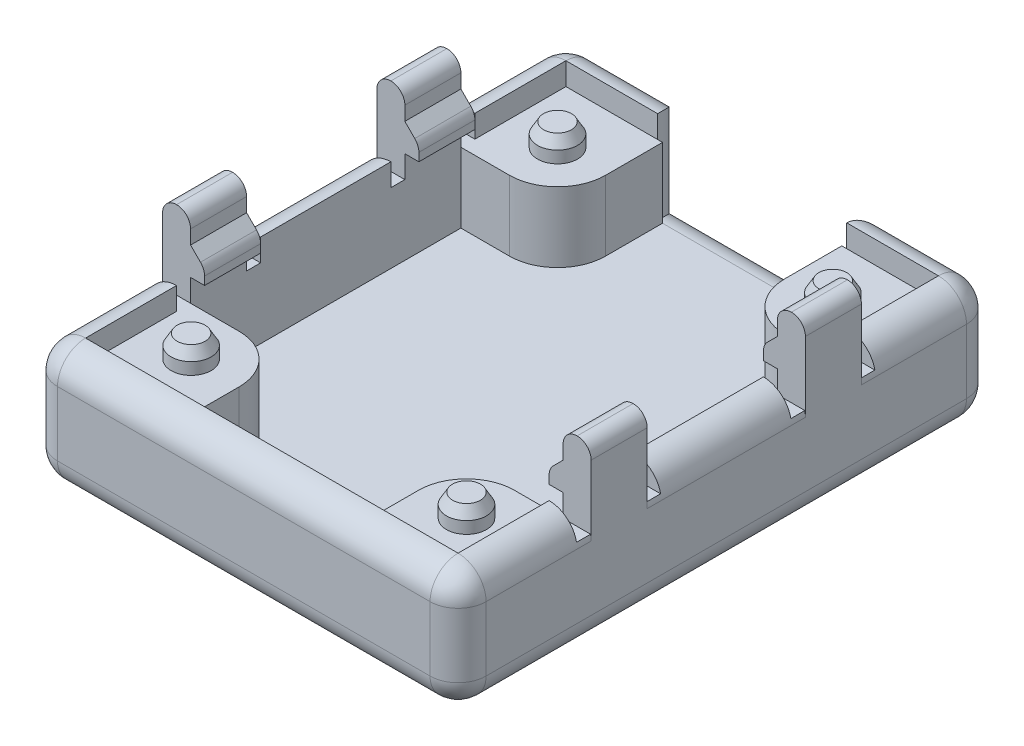
SolidWorks part; units mm, degrees
ref_plane "Front Plane" through (0, 0, 0) normal (0, 0, 1) x (1, 0, 0)
ref_plane "Top Plane" through (0, 0, 0) normal (0, 1, 0) x (1, 0, 0)
ref_plane "Right Plane" through (0, 0, 0) normal (1, 0, 0) x (0, 0, -1)
sketch "top right screw hole" plane through (0, 0, 0) normal (0, 1, 0) x (1, 0, 0)
  line L0 (-8.4, 0) -> (8.4, 0) construction
  line L1 (0, 11.65) -> (0, -11.65) construction
  circle A0 centre (9.83, 13.08) radius 1.43
  point P2 (0, 0)
  point P6 (0, 0)
  point P9 (9.83, 11.65)
  point P10 (8.4, 13.08)
  point P11 (0, 0)
  point P12 (0, 0)
  point P13 (0, 0)
  dimension "D3" = 2.86
  dimension "D1" = 16.8
  dimension "D2" = 23.3
sketch "all screw holes" plane through (0, 0, 0) normal (0, 1, 0) x (1, 0, 0)
  line L0 (0, -4.73) -> (0, 4.73) construction
  line L1 (-4.73, 0) -> (4.73, 0) construction
  circle A0 centre (9.83, 13.08) radius 1.43 construction
  circle A1 centre (9.83, 13.08) radius 1.43
  circle A2 centre (-9.83, 13.08) radius 1.43
  circle A3 centre (-9.83, -13.08) radius 1.43
  circle A4 centre (9.83, -13.08) radius 1.43
  point P13 (0, 0)
sketch "pcb" plane through (0, 0, 0) normal (0, 1, 0) x (1, 0, 0)
  line L1 (-13.3, -17.15) -> (13.3, -17.15)
  line L2 (-13.3, -17.15) -> (-13.3, 17.15)
  line L3 (-13.3, 17.15) -> (13.3, 17.15)
  line L4 (13.3, -17.15) -> (13.3, 17.15)
  line L5 (-13.3, -17.15) -> (13.3, 17.15) construction
  line L6 (-13.3, 17.15) -> (13.3, -17.15) construction
  point P0 (0, 0)
  point P6 (0, 0)
  dimension "D1" = 26.6
  dimension "D2" = 34.3
sketch "wires" plane through (0, 0, 0) normal (0, 1, 0) x (1, 0, 0)
  line L0 (-13.3, 17.15) -> (13.3, 17.15) construction
  line L1 (-6.75, 17.15) -> (6.75, 17.15)
  line L2 (-6.75, 17.15) -> (-6.75, 21.7884)
  line L3 (-6.75, 21.7884) -> (6.75, 21.7884)
  line L4 (6.75, 17.15) -> (6.75, 21.7884)
  line L5 (-6.75, 17.15) -> (6.75, 21.7884) construction
  line L6 (-6.75, 21.7884) -> (6.75, 17.15) construction
  point P0 (0, 19.4692)
  point P5 (0, 0)
  point P6 (0, 0)
  point P8 (0, 0)
  point P9 (0, 22.0718)
  point P12 (0, 0)
  dimension "D1" = 13.5
sketch "room for bottom wires" plane through (0, 0, 0) normal (1, 0, 0) x (0, 0, -1)
  line L0 (-17.15, 0) -> (17.15, 0) construction
  line L1 (-17.15, 0) -> (17.15, 0)
  line L2 (-17.15, 0) -> (-17.15, -5)
  line L3 (-17.15, -5) -> (17.15, -5)
  line L4 (17.15, 0) -> (17.15, -5)
  line L5 (-17.15, 0) -> (17.15, 0) construction
  point P8 (0, 0)
  point P10 (0, 0)
  point P12 (0, 0)
  dimension "D1" = 5
sketch "Sketch6" plane through (0, 0, 0) normal (0, 1, 0) x (1, 0, 0)
  line L8 (-15.3, -19.15) -> (15.3, -19.15)
  line L9 (15.3, -19.15) -> (15.3, 19.15)
  line L10 (15.3, 19.15) -> (-15.3, 19.15)
  line L11 (-15.3, 19.15) -> (-15.3, -19.15)
  line L12 (-15.3, -19.15) -> (15.3, -19.15)
  line L13 (15.3, -19.15) -> (15.3, 19.15)
  line L14 (15.3, 19.15) -> (-15.3, 19.15)
  line L15 (-15.3, 19.15) -> (-15.3, -19.15)
  dimension "D1" = 2
extrude "base" add sketch "Sketch6" against normal blind 2 from vertex at -5 starting at point (0, -5, 17.15)
sketch "pcb thickness" plane through (0, 0, 0) normal (1, 0, 0) x (0, 0, -1)
  line L0 (16.83, 0) -> (-16.83, 0) construction
  line L1 (-17.15, 0) -> (17.15, 0)
  line L2 (-17.15, 0) -> (-17.15, 1.6)
  line L3 (-17.15, 1.6) -> (17.15, 1.6)
  line L4 (17.15, 0) -> (17.15, 1.6)
  line L5 (-17.15, 0) -> (17.15, 1.6) construction
  line L6 (-17.15, 1.6) -> (17.15, 0) construction
  point P0 (0, 0.8)
  point P9 (0, 0)
  point P10 (0, 0)
  dimension "D1" = 1.6
sketch "Sketch8" plane through (0, -5, 0) normal (0, 1, 0) x (1, 0, 0)
  line L0 (6.75, 17.15) -> (6.75, 21.7884) construction
  line L1 (-6.75, 17.15) -> (-6.75, 21.7884) construction
  line L2 (6.75, 17.15) -> (6.75, 19.15)
  line L3 (-6.75, 17.15) -> (-6.75, 19.15)
  line L4 (-15.3, 19.15) -> (-15.3, -19.15)
  line L5 (-15.3, -19.15) -> (15.3, -19.15)
  line L6 (15.3, -19.15) -> (15.3, 19.15)
  line L7 (15.3, 19.15) -> (-15.3, 19.15)
  line L8 (-15.3, 19.15) -> (-15.3, -19.15)
  line L9 (-15.3, -19.15) -> (15.3, -19.15)
  line L10 (15.3, -19.15) -> (15.3, 19.15)
  line L11 (15.3, 19.15) -> (6.75, 19.15)
  line L12 (-13.3, -17.15) -> (13.3, -17.15)
  line L13 (13.3, -17.15) -> (13.3, 17.15)
  line L14 (13.3, 17.15) -> (-13.3, 17.15)
  line L15 (-13.3, 17.15) -> (-13.3, -17.15)
  line L16 (-13.3, -17.15) -> (13.3, -17.15)
  line L17 (13.3, -17.15) -> (13.3, 17.15)
  line L18 (13.3, 17.15) -> (6.75, 17.15)
  line L19 (-13.3, 17.15) -> (-13.3, -17.15)
  line L20 (-6.75, 19.15) -> (-15.3, 19.15)
  line L21 (-6.75, 17.15) -> (-13.3, 17.15)
  dimension "D1" = 0
  dimension "D2" = 0
extrude "walls" add sketch "Sketch8" along normal up to vertex (6.6 mm away) up to point (0, 1.6, -17.15)
sketch "Sketch9" plane through (0, 0, 0) normal (0, 1, 0) x (1, 0, 0)
  line L0 (6.4, 13.08) -> (6.4, 17.15)
  line L2 (-13.3, 17.15) -> (13.3, 17.15) construction
  line L4 (6.4, 17.15) -> (13.3, 17.15)
  line L5 (13.3, 17.15) -> (13.3, 9.65)
  line L6 (13.3, -17.15) -> (13.3, 17.15) construction
  line L7 (13.3, 9.65) -> (9.83, 9.65)
  line L8 (0, -4.73) -> (0, 4.73) construction
  line L9 (-13.3, 9.65) -> (-9.83, 9.65)
  line L10 (-13.3, 17.15) -> (-13.3, 9.65)
  line L11 (-6.4, 17.15) -> (-13.3, 17.15)
  line L12 (-6.4, 13.08) -> (-6.4, 17.15)
  line L13 (-4.73, 0) -> (4.73, 0) construction
  line L14 (-6.4, -13.08) -> (-6.4, -17.15)
  line L15 (-6.4, -17.15) -> (-13.3, -17.15)
  line L16 (-13.3, -17.15) -> (-13.3, -9.65)
  line L17 (-13.3, -9.65) -> (-9.83, -9.65)
  line L18 (13.3, -9.65) -> (9.83, -9.65)
  line L19 (13.3, -17.15) -> (13.3, -9.65)
  line L20 (6.4, -17.15) -> (13.3, -17.15)
  line L21 (6.4, -13.08) -> (6.4, -17.15)
  arc A5 (-6.4, 13.08) -> (-9.83, 9.65) centre (-9.83, 13.08) cw
  circle A10 centre (9.83, 13.08) radius 3.43
  arc A12 (6.4, 13.08) -> (9.83, 9.65) centre (9.83, 13.08) ccw
  arc A13 (6.4, -13.08) -> (9.83, -9.65) centre (9.83, -13.08) cw
  arc A15 (-6.4, -13.08) -> (-9.83, -9.65) centre (-9.83, -13.08) ccw
  dimension "D1" = 2
extrude "supports" add sketch "Sketch9" against normal up to next
sketch "Sketch10" plane through (0, 0, 0) normal (0, 1, 0) x (1, 0, 0)
  circle A1 centre (9.83, -13.08) radius 1.43
  circle A2 centre (9.83, -13.08) radius 1.43
  circle A3 centre (-9.83, -13.08) radius 1.43
  circle A4 centre (-9.83, -13.08) radius 1.43
  circle A5 centre (-9.83, 13.08) radius 1.43
  circle A6 centre (-9.83, 13.08) radius 1.43
  circle A7 centre (9.83, 13.08) radius 1.43
  circle A8 centre (9.83, 13.08) radius 1.43
  dimension "D1" = 0
  dimension "D2" = 0
  dimension "D3" = 0
  dimension "D4" = 0
extrude "inserts" add sketch "Sketch10" along normal up to vertex (1.6 mm away) up to point (0, 1.6, -17.15)
sketch "clips" plane through (0, 0, 0) normal (0, 0, 1) x (1, 0, 0)
  line L0 (-15.3, 1.6) -> (-15.3, 5.6)
  line L1 (-15.3, 5.6) -> (-13.3, 5.6)
  line L2 (-13.3, 5.6) -> (-13.3, 3.6)
  line L4 (-15.3, 1.6) -> (15.3, 1.6) construction
  line L5 (-12.3, 1.6) -> (-15.3, 1.6)
  line L6 (-12.3, 1.6) -> (-12.3, 2.6)
  line L7 (-12.3, 2.6) -> (-13.3, 3.6)
  line L8 (0, -4.73) -> (0, 4.73) construction
  line L9 (12.3, 2.6) -> (13.3, 3.6)
  line L10 (12.3, 1.6) -> (12.3, 2.6)
  line L11 (12.3, 1.6) -> (15.3, 1.6)
  line L12 (13.3, 5.6) -> (13.3, 3.6)
  line L13 (15.3, 5.6) -> (13.3, 5.6)
  line L14 (15.3, 1.6) -> (15.3, 5.6)
  dimension "D1" = 1
  dimension "D2" = 2
  dimension "D3" = 1
  dimension "D4" = 45
sketch "Sketch13" plane through (0, 0, 0) normal (0, 0, 1) x (1, 0, 0)
  line L6 (-15.3, 5.6) -> (-15.3, 1.6)
  line L7 (-13.3, 5.6) -> (-15.3, 5.6)
  line L8 (-13.3, 3.6) -> (-13.3, 5.6)
  line L9 (-12.3, 2.6) -> (-13.3, 3.6)
  line L10 (-12.3, 1.6) -> (-12.3, 2.6)
  line L11 (-15.3, 1.6) -> (-12.3, 1.6)
  line L12 (-15.3, 5.6) -> (-15.3, 1.6)
  line L13 (-13.3, 5.6) -> (-15.3, 5.6)
  line L14 (-13.3, 3.6) -> (-13.3, 5.6)
  line L15 (-12.3, 2.6) -> (-13.3, 3.6)
  line L16 (-12.3, 1.6) -> (-12.3, 2.6)
  line L17 (-15.3, 1.6) -> (-12.3, 1.6)
  line L18 (15.3, 5.6) -> (13.3, 5.6)
  line L19 (15.3, 1.6) -> (15.3, 5.6)
  line L20 (12.3, 1.6) -> (15.3, 1.6)
  line L21 (12.3, 2.6) -> (12.3, 1.6)
  line L22 (13.3, 3.6) -> (12.3, 2.6)
  line L23 (13.3, 5.6) -> (13.3, 3.6)
  line L24 (15.3, 5.6) -> (13.3, 5.6)
  line L25 (15.3, 1.6) -> (15.3, 5.6)
  line L26 (12.3, 1.6) -> (15.3, 1.6)
  line L27 (12.3, 2.6) -> (12.3, 1.6)
  line L28 (13.3, 3.6) -> (12.3, 2.6)
  line L29 (13.3, 5.6) -> (13.3, 3.6)
  dimension "D1" = 0
  dimension "D2" = 0
extrude "Boss-Extrude5" add sketch "Sketch13" against normal blind 4 from surface at 9.65 starting at face at (-11.565, -2.5, 9.65)
sketch "Sketch15" plane through (0, 0, 0) normal (0, 0, 1) x (1, 0, 0)
  line L0 (-15.3, 1.6) -> (-15.3, 5.6)
  line L1 (-15.3, 5.6) -> (-13.3, 5.6)
  line L2 (-13.3, 5.6) -> (-13.3, 3.6)
  line L5 (-12.3, 1.6) -> (-15.3, 1.6)
  line L6 (-12.3, 1.6) -> (-12.3, 2.6)
  line L7 (-12.3, 2.6) -> (-13.3, 3.6)
  line L9 (12.3, 2.6) -> (13.3, 3.6)
  line L10 (12.3, 1.6) -> (12.3, 2.6)
  line L11 (12.3, 1.6) -> (15.3, 1.6)
  line L12 (13.3, 5.6) -> (13.3, 3.6)
  line L13 (15.3, 5.6) -> (13.3, 5.6)
  line L14 (15.3, 1.6) -> (15.3, 5.6)
  dimension "D1" = 1
  dimension "D2" = 2
  dimension "D4" = 45
extrude "Boss-Extrude7" add sketch "Sketch15" along normal blind 4 from surface at -9.65 starting at face at (-11.565, -2.5, -9.65)
sketch "Sketch16" plane through (0, 0, 0) normal (0, 1, 0) x (1, 0, 0)
  line L0 (-13.3, -17.15) -> (-13.3, 17.15) construction
  line L1 (-15.3, 9.65) -> (-13.3, 9.65)
  line L2 (-15.3, 9.65) -> (-15.3, 10.65)
  line L3 (-15.3, 10.65) -> (-13.3, 10.65)
  line L4 (-13.3, 9.65) -> (-13.3, 10.65)
  line L5 (0, -6.93) -> (0, 6.93) construction
  line L6 (-15.3, 5.65) -> (-13.3, 5.65)
  line L7 (-15.3, 5.65) -> (-15.3, 4.65)
  line L8 (-15.3, 4.65) -> (-13.3, 4.65)
  line L9 (-13.3, 5.65) -> (-13.3, 4.65)
  line L11 (13.3, 5.65) -> (13.3, 4.65)
  line L12 (15.3, 4.65) -> (13.3, 4.65)
  line L13 (15.3, 5.65) -> (15.3, 4.65)
  line L14 (15.3, 5.65) -> (13.3, 5.65)
  line L15 (13.3, 9.65) -> (13.3, 10.65)
  line L16 (15.3, 10.65) -> (13.3, 10.65)
  line L17 (15.3, 9.65) -> (15.3, 10.65)
  line L18 (15.3, 9.65) -> (13.3, 9.65)
  line L19 (-6.93, 0) -> (6.93, 0) construction
  line L20 (15.3, -9.65) -> (13.3, -9.65)
  line L21 (15.3, -9.65) -> (15.3, -10.65)
  line L22 (15.3, -10.65) -> (13.3, -10.65)
  line L23 (13.3, -9.65) -> (13.3, -10.65)
  line L24 (15.3, -5.65) -> (13.3, -5.65)
  line L25 (15.3, -5.65) -> (15.3, -4.65)
  line L26 (15.3, -4.65) -> (13.3, -4.65)
  line L27 (13.3, -5.65) -> (13.3, -4.65)
  line L28 (-13.3, -5.65) -> (-13.3, -4.65)
  line L29 (-15.3, -4.65) -> (-13.3, -4.65)
  line L30 (-15.3, -5.65) -> (-15.3, -4.65)
  line L31 (-15.3, -5.65) -> (-13.3, -5.65)
  line L32 (-13.3, -9.65) -> (-13.3, -10.65)
  line L33 (-15.3, -10.65) -> (-13.3, -10.65)
  line L34 (-15.3, -9.65) -> (-15.3, -10.65)
  line L35 (-15.3, -9.65) -> (-13.3, -9.65)
  dimension "D1" = 1
  dimension "D2" = 1
extrude "Cut-Extrude1" cut sketch "Sketch16" along normal up to next
fillet "Fillet1" radius 2 20 edges at (-6.75, -1.7, -19.15) (-11.025, 1.6, -19.15) (0, -7, -19.15) (11.025, 1.6, -19.15) (6.75, -1.7, -19.15) (0, -5, -19.15) (-15.3, 1.6, 0) (-15.3, 1.6, 14.9) (-15.3, -7, 0) (-15.3, -2.7, -19.15) (-15.3, 1.6, -14.9) (0, -7, 19.15) (-15.3, -2.7, 19.15) (0, 1.6, 19.15) (15.3, 1.6, 0) (15.3, 1.6, -14.9) (15.3, -2.7, -19.15) (15.3, -7, 0) (15.3, -2.7, 19.15) (15.3, 1.6, 14.9)
fillet "Fillet2" radius 1 12 edges at (12.3, 2.6, 7.65) (12.3, 2.6, -7.65) (-12.3, 2.6, -7.65) (-12.3, 2.6, 7.65) (15.3, 5.6, -7.65) (13.3, 5.6, -7.65) (15.3, 5.6, 7.65) (13.3, 5.6, 7.65) (-13.3, 5.6, -7.65) (-15.3, 5.6, -7.65) (-15.3, 5.6, 7.65) (-13.3, 5.6, 7.65)
chamfer "Chamfer1" distance 0.75 angle 30 4 edges at (9.83, 1.6, -11.65) (9.83, 1.6, 14.51) (-9.83, 1.6, 14.51) (-9.83, 1.6, -11.65)
